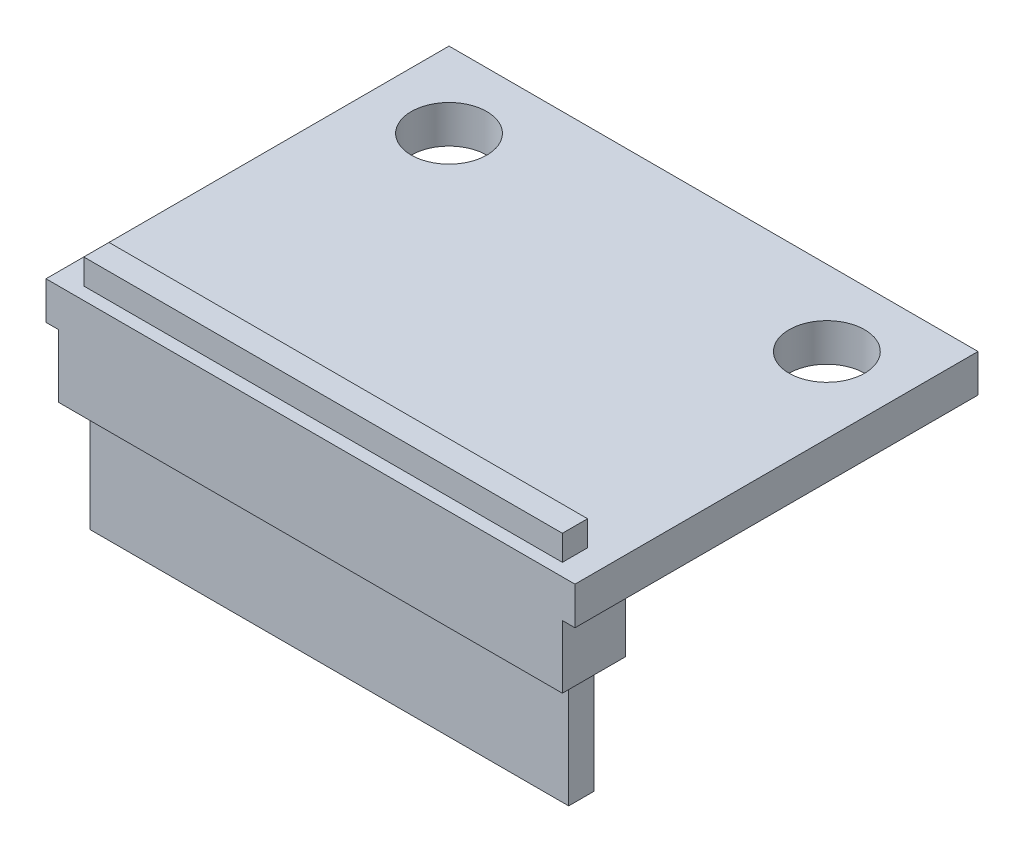
SolidWorks part; units mm, degrees
ref_plane "Front" through (0, 0, 0) normal (0, 0, 1) x (1, 0, 0)
ref_plane "Top" through (0, 0, 0) normal (0, 1, 0) x (1, 0, 0)
ref_plane "Right" through (0, 0, 0) normal (1, 0, 0) x (0, 0, -1)
sketch "Эскиз1" plane through (0, 0, 0) normal (0, 1, 0) x (1, 0, 0)
  line L0 (0, -8) -> (0, 8) construction
  line L1 (-10.5, 8) -> (10.5, 8)
  line L2 (-10.5, 8) -> (-10.5, -8)
  line L3 (-10.5, -8) -> (10.5, -8)
  line L4 (10.5, 8) -> (10.5, -8)
  line L5 (-10.5, 8) -> (10.5, -8) construction
  line L6 (-10.5, -8) -> (10.5, 8) construction
  line L8 (-9.5, -6.5) -> (9.5, -6.5)
  line L9 (-9.5, -6.5) -> (-9.5, -7.5)
  line L10 (-9.5, -7.5) -> (9.5, -7.5)
  line L11 (9.5, -6.5) -> (9.5, -7.5)
  line L12 (-9.5, -6.5) -> (9.5, -7.5) construction
  line L13 (-9.5, -7.5) -> (9.5, -6.5) construction
  circle A0 centre (-7.5, 5) radius 1.5
  circle A1 centre (7.5, 5) radius 1.5
  point P0 (0, 0)
  point P12 (0, -7)
  dimension "D3" = 3
  dimension "D1" = 21
  dimension "D2" = 16
  dimension "D4" = 3
  dimension "D5" = 3
  dimension "D6" = 19
  dimension "D7" = 1
  dimension "D8" = 0.5
extrude "Бобышка-Вытянуть2" add sketch "Эскиз1" against normal blind 1.5 contours L4 L1 L2 L3 A1 A0 L8 L11 L10 L9 | L8 L11 L10 L9 region at (0, 0, -0.2058)
extrude "Бобышка-Вытянуть3" add sketch "Эскиз1<4>" along normal blind 1 contours L8 L11 L10 L9
sketch "Эскиз1<4>" plane through (0, 0, 0) normal (0, 1, 0) x (1, 0, 0) same geometry as "Эскиз1"
sketch "Эскиз3" plane through (0, -1.5, 0) normal (0, -1, 0) x (1, 0, 0)
  line L0 (0, -8) -> (0, 8) construction
  line L1 (-10.5, -8) -> (10.5, -8) construction
  line L2 (-10.5, 8) -> (10.5, 8) construction
  line L4 (-10, 8) -> (10, 8)
  line L5 (-10, 8) -> (-10, 5.5)
  line L6 (-10, 5.5) -> (10, 5.5)
  line L7 (10, 8) -> (10, 5.5)
  line L8 (-10, 8) -> (10, 5.5) construction
  line L9 (-10, 5.5) -> (10, 8) construction
  line L10 (-9.5, 7.25) -> (9.5, 7.25)
  line L11 (-9.5, 7.25) -> (-9.5, 6.25)
  line L12 (-9.5, 6.25) -> (9.5, 6.25)
  line L13 (9.5, 7.25) -> (9.5, 6.25)
  line L14 (-9.5, 7.25) -> (9.5, 6.25) construction
  line L15 (-9.5, 6.25) -> (9.5, 7.25) construction
  point P6 (0, 6.75)
  point P11 (0, 6.75)
  dimension "D1" = 1
  dimension "D2" = 2.5
  dimension "D3" = 19
  dimension "D4" = 20
extrude "Бобышка-Вытянуть4" add sketch "Эскиз3" along normal blind 7 contours L13 L10 L11 L12 region at (0, -1.5, 6.75)
extrude "Бобышка-Вытянуть5" add sketch "Эскиз3<3>" along normal blind 2.5 contours L6 L7 L4 L5
sketch "Эскиз3<3>" plane through (0, -1.5, 0) normal (0, -1, 0) x (1, 0, 0) same geometry as "Эскиз3"
